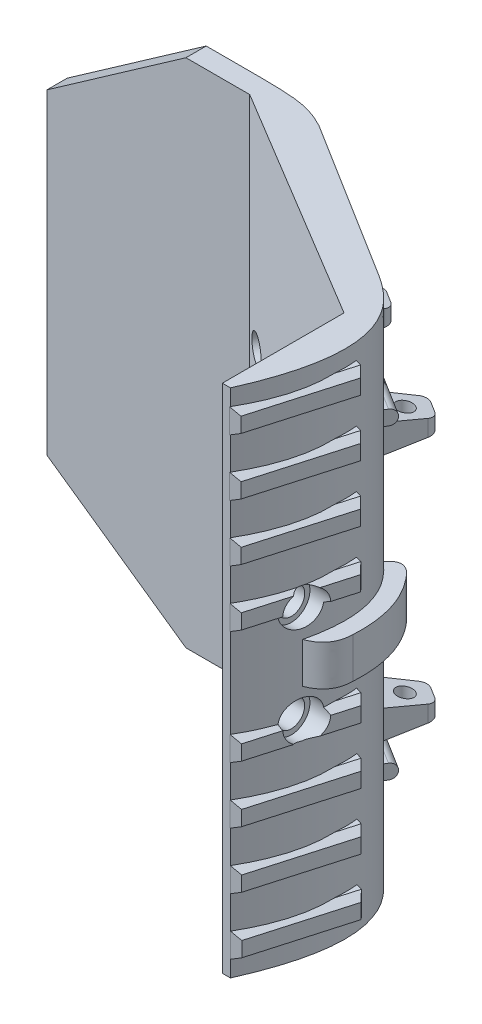
SolidWorks part; units mm, degrees
ref_plane "前视基准面" through (0, 0, 0) normal (0, 0, 1) x (1, 0, 0)
ref_plane "上视基准面" through (0, 0, 0) normal (0, 1, 0) x (1, 0, 0)
ref_plane "右视基准面" through (0, 0, 0) normal (1, 0, 0) x (0, 0, -1)
sketch "草图1" plane through (0, 0, 0) normal (0, 1, 0) x (1, 0, 0)
  line L5 (44.4388, -6.0197) -> (44.4388, -21.0197)
  line L6 (44.4388, -21.0197) -> (45.4388, -21.0197)
  line L7 (44.4388, -6.0197) -> (15.3139, 11.4803)
  line L8 (12.0784, 13.9803) -> (10.0784, 13.9803)
  line L9 (41.6518, 0.7146) -> (22.8495, 12.4582)
  line L10 (10.0784, 13.9803) -> (-9.6861, 13.9803)
  line L11 (-9.6861, 11.4803) -> (15.3139, 11.4803)
  line L12 (-9.6861, 13.9803) -> (-9.6861, 11.4803)
  line L13 (-35.8192, -203.5283) -> (126.6968, 161.4888) construction
  line L14 (85.2699, -26.5286) -> (-1.9663, 27.9577) construction
  spline S0 degree 3 poles (12.0784, 13.9803) (18.0822, 13.9803) (20.027, 13.9726) (22.8495, 12.4582) knots 0 0 0 0 0.428174 0.428174 0.428174 0.428174
  spline S1 degree 3 poles (41.6518, 0.7146) (45.3405, -1.5893) (52.3106, -5.5855) (45.4388, -21.0197) knots 0.746299 0.746299 0.746299 0.746299 1 1 1 1
  dimension "D3" = 121
  dimension "D2" = 20
  dimension "D6" = 114
  dimension "D7" = 180
  dimension "D1" = 1
  dimension "D4" = 2
  dimension "D5" = 35
  dimension "D8" = 2.5
  dimension "D9" = 25
extrude "凸台-拉伸1" add sketch "草图1" along normal blind 63
sketch "草图2" plane through (12.0098, 0, -19.2285) normal (0.5297, 0, -0.8482) x (-0.8482, 0, -0.5297)
  line L0 (-12.7803, 31.5) -> (-34.9487, 31.5) construction
  line L1 (-12.7803, 63) -> (-12.7803, 0) construction
  line L2 (-34.9487, 63) -> (-34.9487, 0) construction
  line L4 (-31.9487, 24.5) -> (-17.9487, 24.5)
  line L5 (-31.9487, 24.5) -> (-31.9487, 38.5)
  line L6 (-31.9487, 38.5) -> (-17.9487, 38.5)
  line L7 (-17.9487, 24.5) -> (-17.9487, 38.5)
  line L8 (-31.9487, 24.5) -> (-17.9487, 38.5) construction
  line L9 (-31.9487, 38.5) -> (-17.9487, 24.5) construction
  point P6 (-24.9487, 31.5)
  dimension "D1" = 14
  dimension "D2" = 14
  dimension "D3" = 3
extrude "凸台-拉伸2" add sketch "草图2" along normal blind 1 draft 25
sketch "草图6" plane through (0, 0, 0) normal (0, -1, 0) x (1, 0, 0)
  line L0 (13.0784, -13.9799) -> (24.6291, -11.9432)
  line L1 (15.3139, -11.4803) -> (44.4388, 6.0197) construction
  spline S0 degree 3 poles (22.8495, -12.4582) (20.027, -13.9726) (18.0822, -13.9803) (12.0784, -13.9803) knots 0 0 0 0 0.428174 0.428174 0.428174 0.428174 construction
  dimension "D1" = 21
  dimension "D2" = 1
ref_plane "基准面2" through (2.7851, 0, -15.7949) normal (0.1736, 0, -0.9848) x (0.9848, 0, 0.1736)
sketch "草图7" plane through (2.7851, 0, -15.7949) normal (0.1736, 0, -0.9848) x (0.9848, 0, 0.1736)
  line L1 (11.4673, -18.5) -> (22.4673, -18.5)
  line L2 (11.4673, -18.5) -> (11.4673, -44.5)
  line L3 (11.4673, -44.5) -> (22.4673, -44.5)
  line L4 (22.4673, -18.5) -> (22.4673, -44.5)
  line L5 (9.4673, -63) -> (9.4673, 0) construction
  line L7 (38.1132, -24.5) -> (25.1315, -24.5) construction
  line L8 (25.1315, -38.5) -> (38.1132, -38.5) construction
  dimension "D1" = 6
  dimension "D2" = 6
  dimension "D3" = 11
  dimension "D4" = 2
sketch "草图3" plane through (12.5395, 0, -20.0767) normal (0.5297, 0, -0.8482) x (-0.8482, 0, -0.5297)
  line L0 (-18.415, 31.5) -> (-31.4824, 31.5) construction
  line L1 (-18.415, 24.9663) -> (-18.415, 38.0337) construction
  line L2 (-31.4824, 38.0337) -> (-31.4824, 24.9663) construction
  line L3 (-24.9487, 38.0337) -> (-24.9487, 24.9663) construction
  line L4 (-18.415, 38.0337) -> (-31.4824, 38.0337) construction
  line L5 (-31.4824, 24.9663) -> (-18.415, 24.9663) construction
  line L6 (-21.7668, 34.682) -> (-28.1307, 28.318) construction
  line L7 (-20.7061, 33.6213) -> (-27.0701, 27.2574)
  line L8 (-22.8274, 35.7426) -> (-29.1914, 29.3787)
  line L9 (-21.7668, 28.318) -> (-28.1307, 34.682) construction
  line L10 (-22.8274, 27.2574) -> (-29.1914, 33.6213)
  line L11 (-20.7061, 29.3787) -> (-27.0701, 35.7426)
  arc A0 (-20.7061, 33.6213) -> (-22.8274, 35.7426) centre (-21.7668, 34.682) ccw
  arc A1 (-29.1914, 29.3787) -> (-27.0701, 27.2574) centre (-28.1307, 28.318) ccw
  arc A2 (-22.8274, 27.2574) -> (-20.7061, 29.3787) centre (-21.7668, 28.318) ccw
  arc A3 (-27.0701, 35.7426) -> (-29.1914, 33.6213) centre (-28.1307, 34.682) ccw
  point P14 (-24.9487, 31.5)
  point P19 (-24.9487, 31.5)
  dimension "D1" = 3
  dimension "D2" = 3
  dimension "D3" = 9
  dimension "D4" = 9
extrude "切除-拉伸1" cut sketch "草图3" against normal blind 0.6 contours L7 A0 L8 L11 | L7 L11 L8 L10 | L10 A2 L11 L7 | L8 A1 L7 L10 | L11 A3 L10 L8 region at (31.5395, 34.0473, -8.2096) region at (31.5395, 28.9527, -8.2096) region at (33.7, 31.5, -6.8602) region at (35.8605, 28.9527, -5.5108) region at (35.8605, 34.0473, -5.5108)
ref_plane "基准面1" through (10.1606, 0, -16.91) normal (-0.515, 0, 0.8572) x (0.8572, 0, 0.515)
extrude "凸台-拉伸4" add sketch "草图7" along normal blind 2 draft 35 and the other way blind 2
sketch "草图4" plane through (9.1305, 0, -15.1957) normal (-0.515, 0, 0.8572) x (0.8572, 0, 0.515)
  line L0 (41.1919, 31.5) -> (-14.9499, 31.5) construction
  line L1 (41.1919, 63) -> (41.1919, 0) construction
  line L2 (3.1528, 63) -> (3.1528, 0) construction
  circle A0 centre (9.6528, 25.5) radius 1.65
  circle A1 centre (9.6528, 37.5) radius 1.65
  dimension "D1" = 3.3
  dimension "D2" = 12
  dimension "D3" = 6.5
extrude "切除-拉伸2" cut sketch "草图4" against normal through all
sketch "草图5" plane through (10.1606, 0, -16.91) normal (-0.515, 0, 0.8572) x (0.8572, 0, 0.515)
  circle A0 centre (9.6528, 25.5) radius 2.3
  circle A1 centre (9.6528, 37.5) radius 2.3
  dimension "D1" = 4.6
extrude "切除-拉伸3" cut sketch "草图5" against normal through all
ref_plane "基准面3" through (2.7851, 0, -15.7949) normal (-0.1736, 0, 0.9848) x (0.9848, 0, 0.1736)
sketch "草图9" plane through (0, 0, 0) normal (0, -1, 0) x (1, 0, 0)
  line L0 (45.4388, 21.0197) -> (53.1155, -5.7522) construction
  line L1 (44.4388, 21.0197) -> (45.4388, 21.0197) construction
  dimension "D1" = 106
ref_plane "基准面4" through (47.5559, 0, 13.6364) normal (-0.9613, 0, -0.2756) x (-0.2756, 0, 0.9613)
sketch "草图10" plane through (47.5559, 0, 13.6364) normal (-0.9613, 0, -0.2756) x (-0.2756, 0, 0.9613)
  line L0 (-5.3616, 67.0628) -> (-5.3616, -5.3831) construction
  line L1 (7.6808, 63) -> (7.6808, 0) construction
  line L2 (-5.3616, 5) -> (7.6808, 5)
  line L3 (-5.3616, 5) -> (-5.3616, 2)
  line L4 (-5.3616, 2) -> (7.6808, 2)
  line L5 (7.6808, 5) -> (7.6808, 2)
  line L6 (-5.3514, 9) -> (7.691, 9)
  line L11 (-5.3514, 12) -> (7.691, 12)
  line L12 (-5.3514, 12) -> (-5.3514, 9)
  line L13 (7.691, 12) -> (7.691, 9)
  line L14 (-5.3514, 31.5) -> (-5.3514, 1.6169) construction
  line L15 (-5.3412, 16) -> (7.7012, 16)
  line L16 (-5.3412, 19) -> (7.7012, 19)
  line L17 (-5.3412, 19) -> (-5.3412, 16)
  line L18 (7.7012, 19) -> (7.7012, 16)
  line L19 (-5.3412, 31.5) -> (-5.3412, 8.6169) construction
  line L20 (-5.331, 23) -> (7.7115, 23)
  line L21 (-5.331, 26) -> (7.7115, 26)
  line L22 (-5.331, 26) -> (-5.331, 23)
  line L23 (7.7115, 26) -> (7.7115, 23)
  line L24 (-5.331, 31.5) -> (-5.331, 15.6169) construction
  line L25 (-5.3207, 30) -> (7.7217, 30)
  line L26 (-5.3207, 33) -> (7.7217, 33)
  line L27 (-5.3207, 33) -> (-5.3207, 30)
  line L28 (7.7217, 33) -> (7.7217, 30)
  line L29 (-5.3207, 33) -> (-5.3207, 22.6169) construction
  line L30 (-5.3105, 37) -> (7.7319, 37)
  line L31 (-5.3105, 40) -> (7.7319, 40)
  line L32 (-5.3105, 40) -> (-5.3105, 37)
  line L33 (7.7319, 40) -> (7.7319, 37)
  line L34 (-5.3105, 40) -> (-5.3105, 29.6169) construction
  line L35 (-5.3003, 44) -> (7.7421, 44)
  line L36 (-5.3003, 47) -> (7.7421, 47)
  line L37 (-5.3003, 47) -> (-5.3003, 44)
  line L38 (7.7421, 47) -> (7.7421, 44)
  line L39 (-5.3003, 47) -> (-5.3003, 36.6169) construction
  line L40 (-5.2901, 51) -> (7.7523, 51)
  line L41 (-5.2901, 54) -> (7.7523, 54)
  line L42 (-5.2901, 54) -> (-5.2901, 51)
  line L43 (7.7523, 54) -> (7.7523, 51)
  line L44 (-5.2901, 54) -> (-5.2901, 43.6169) construction
  line L45 (-5.2799, 58) -> (7.7625, 58)
  line L46 (-5.2799, 61) -> (7.7625, 61)
  line L47 (-5.2799, 61) -> (-5.2799, 58)
  line L48 (7.7625, 61) -> (7.7625, 58)
  line L49 (-5.2799, 61) -> (-5.2799, 50.6168) construction
  line L52 (7.6808, 31.5) -> (-12.1158, 31.5) construction
  point P9 (7.7217, 31.5)
  dimension "D1" = 3
  dimension "D2" = 9
extrude "凸台-拉伸6" add sketch "草图10" against normal blind 1 draft 30 contours L5 L2 L3 L4 | L13 L11 L12 L6 | L23 L21 L22 L20 | L38 L36 L37 L35 | L43 L41 L42 L40 | L48 L46 L47 L45 | L16 L18 L15 L17 | L31 L33 L30 L32 region at (47.2363, 3.5, 14.7511) region at (47.2335, 10.5, 14.761) region at (47.2278, 24.5, 14.7806) region at (47.2194, 45.5, 14.81) region at (47.2166, 52.5, 14.8198) region at (47.2138, 59.5, 14.8297)
sketch "草图11" plane through (47.5559, 0, 13.6364) normal (-0.9613, 0, -0.2756) x (-0.2756, 0, 0.9613)
  line L0 (-2.6974, 2) -> (-2.6974, 5) construction
  line L1 (-2.6974, 5) -> (-5.3616, 5) construction
  line L2 (-5.3616, 5) -> (-5.3616, 2) construction
  line L3 (-5.3616, 2) -> (-2.6974, 2) construction
  line L4 (-2.6974, 9) -> (-2.6974, 12) construction
  line L5 (-2.6974, 12) -> (-5.3514, 12) construction
  line L6 (-5.3514, 12) -> (-5.3514, 9) construction
  line L7 (-5.3514, 9) -> (-2.6974, 9) construction
  line L8 (-2.6974, 16) -> (-2.6974, 19) construction
  line L9 (-2.6974, 19) -> (-5.3412, 19) construction
  line L10 (-5.3412, 19) -> (-5.3412, 16) construction
  line L11 (-5.3412, 16) -> (-2.6974, 16) construction
  line L12 (-2.6974, 23) -> (-2.6974, 26) construction
  line L13 (-2.6974, 26) -> (-5.331, 26) construction
  line L14 (-5.331, 26) -> (-5.331, 23) construction
  line L15 (-5.331, 23) -> (-2.6974, 23) construction
  line L16 (-2.6974, 37) -> (-2.6974, 40) construction
  line L17 (-2.6974, 40) -> (-5.3105, 40) construction
  line L18 (-5.3105, 40) -> (-5.3105, 37) construction
  line L19 (-5.3105, 37) -> (-2.6974, 37) construction
  line L20 (-2.6974, 44) -> (-2.6974, 47) construction
  line L21 (-2.6974, 47) -> (-5.3003, 47) construction
  line L22 (-5.3003, 47) -> (-5.3003, 44) construction
  line L23 (-5.3003, 44) -> (-2.6974, 44) construction
  line L24 (-2.6974, 58) -> (-2.6974, 61) construction
  line L25 (-2.6974, 61) -> (-5.2799, 61) construction
  line L26 (-5.2799, 61) -> (-5.2799, 58) construction
  line L27 (-5.2799, 58) -> (-2.6974, 58) construction
  line L28 (-2.6974, 51) -> (-2.6974, 54) construction
  line L29 (-2.6974, 54) -> (-5.2901, 54) construction
  line L30 (-5.2901, 54) -> (-5.2901, 51) construction
  line L31 (-5.2901, 51) -> (-2.6974, 51) construction
  line L32 (-2.6974, 2) -> (-2.6974, 5)
  line L33 (-2.6974, 5) -> (-5.3616, 5)
  line L34 (-5.3616, 5) -> (-5.3616, 2)
  line L35 (-5.3616, 2) -> (-2.6974, 2)
  line L36 (-2.6974, 9) -> (-2.6974, 12)
  line L37 (-2.6974, 12) -> (-5.3514, 12)
  line L38 (-5.3514, 12) -> (-5.3514, 9)
  line L39 (-5.3514, 9) -> (-2.6974, 9)
  line L40 (-2.6974, 16) -> (-2.6974, 19)
  line L41 (-2.6974, 19) -> (-5.3412, 19)
  line L42 (-5.3412, 19) -> (-5.3412, 16)
  line L43 (-5.3412, 16) -> (-2.6974, 16)
  line L44 (-2.6974, 23) -> (-2.6974, 26)
  line L45 (-2.6974, 26) -> (-5.331, 26)
  line L46 (-5.331, 26) -> (-5.331, 23)
  line L47 (-5.331, 23) -> (-2.6974, 23)
  line L48 (-2.6974, 37) -> (-2.6974, 40)
  line L49 (-2.6974, 40) -> (-5.3105, 40)
  line L50 (-5.3105, 40) -> (-5.3105, 37)
  line L51 (-5.3105, 37) -> (-2.6974, 37)
  line L52 (-2.6974, 44) -> (-2.6974, 47)
  line L53 (-2.6974, 47) -> (-5.3003, 47)
  line L54 (-5.3003, 47) -> (-5.3003, 44)
  line L55 (-5.3003, 44) -> (-2.6974, 44)
  line L56 (-2.6974, 58) -> (-2.6974, 61)
  line L57 (-2.6974, 61) -> (-5.2799, 61)
  line L58 (-5.2799, 61) -> (-5.2799, 58)
  line L59 (-5.2799, 58) -> (-2.6974, 58)
  line L60 (-2.6974, 51) -> (-2.6974, 54)
  line L61 (-2.6974, 54) -> (-5.2901, 54)
  line L62 (-5.2901, 54) -> (-5.2901, 51)
  line L63 (-5.2901, 51) -> (-2.6974, 51)
extrude "凸台-拉伸7" add sketch "草图11" along normal up to surface (0.7956 mm away) up to face at (47.2407, 31.5, 13.7652)
sketch "草图12" plane through (44.4388, 0, 0) normal (-1, 0, 0) x (0, 0, 1)
  line L0 (21.0197, 31.5) -> (-9.4999, 31.5) construction
  line L1 (21.0197, 63) -> (21.0197, 0) construction
  line L2 (6.0197, 63) -> (6.0197, 0) construction
  circle A0 centre (14.5197, 25.5) radius 1.65
  circle A1 centre (14.5197, 37.5) radius 1.65
  dimension "D1" = 3.3
  dimension "D2" = 12
  dimension "D3" = 8.5
extrude "切除-拉伸4" cut sketch "草图12" against normal blind 2
sketch "草图13" plane through (46.4388, 0, 0) normal (-1, 0, 0) x (0, 0, 1)
  circle A0 centre (14.5197, 25.5) radius 2.3
  circle A1 centre (14.5197, 37.5) radius 2.3
  dimension "D1" = 4.6
extrude "切除-拉伸5" cut sketch "草图13" against normal through all
chamfer "倒角1" distance 12 angle 55 2 edges at (-9.6861, 63, -12.7303) (-9.6861, 0, -12.7303) first distance on face at (-9.6861, 31.5, -12.7303)
sketch "草图14" plane through (12.0098, 0, -19.2285) normal (0.5297, 0, -0.8482) x (-0.8482, 0, -0.5297)
  line L0 (-34.9487, 31.5) -> (5.0388, 31.5) construction
  line L1 (-34.9487, 63) -> (-34.9487, 0) construction
  line L2 (-34.9487, 63) -> (-12.7803, 63) construction
  line L3 (-27.7803, 54) -> (-17.7803, 54)
  line L4 (-27.7803, 54) -> (-27.7803, 59)
  line L5 (-27.7803, 59) -> (-17.7803, 59)
  line L6 (-17.7803, 54) -> (-17.7803, 59)
  line L7 (-12.7803, 63) -> (-12.7803, 44.3613) construction
  line L8 (-27.7803, 9) -> (-27.7803, 4)
  line L9 (-27.7803, 4) -> (-17.7803, 4)
  line L10 (-17.7803, 9) -> (-17.7803, 4)
  line L11 (-27.7803, 9) -> (-17.7803, 9)
  dimension "D1" = 5
  dimension "D2" = 10
  dimension "D3" = 4
  dimension "D4" = 5
extrude "凸台-拉伸8" add sketch "草图14" along normal blind 1 draft 25
sketch "草图15" plane through (12.0098, 0, -19.2285) normal (0.5297, 0, -0.8482) x (-0.8482, 0, -0.5297)
  line L0 (-34.9487, 31.5) -> (9.9606, 31.5) construction
  line L1 (-20.7803, 45) -> (-15.7803, 45)
  line L2 (-20.7803, 45) -> (-20.7803, 48.5)
  line L3 (-20.7803, 48.5) -> (-15.7803, 48.5)
  line L4 (-15.7803, 45) -> (-15.7803, 48.5)
  line L5 (-34.9487, 63) -> (-34.9487, 0) construction
  line L6 (-12.7803, 63) -> (-12.7803, 44.3613) construction
  line L7 (-26.7803, 63) -> (-26.7803, -8.1652) construction
  line L9 (-15.7803, 18) -> (-15.7803, 14.5)
  line L10 (-20.7803, 18) -> (-15.7803, 18)
  line L11 (-20.7803, 18) -> (-20.7803, 14.5)
  line L12 (-20.7803, 14.5) -> (-15.7803, 14.5)
  line L13 (-37.7803, 45) -> (-37.7803, 48.5)
  line L14 (-32.7803, 45) -> (-32.7803, 48.5)
  line L15 (-32.7803, 18) -> (-32.7803, 14.5)
  line L16 (-32.7803, 14.5) -> (-37.7803, 14.5)
  line L17 (-37.7803, 18) -> (-37.7803, 14.5)
  line L18 (-32.7803, 18) -> (-37.7803, 18)
  line L19 (-32.7803, 48.5) -> (-37.7803, 48.5)
  line L20 (-32.7803, 45) -> (-37.7803, 45)
  line L21 (-34.9487, 63) -> (-12.7803, 63) construction
  dimension "D1" = 5
  dimension "D2" = 3.5
  dimension "D3" = 3
  dimension "D4" = 14
  dimension "D5" = 14.5
extrude "凸台-拉伸9" add sketch "草图15" along normal blind 5 draft 10 and the other way blind 2
fillet "圆角1" radius 1 8 edges at (28.7904, 46.75, -14.6427) (31.5357, 46.75, -12.9281) (43.2091, 46.75, -5.6371) (45.9544, 46.75, -3.9224) (45.9544, 16.25, -3.9224) (43.2091, 16.25, -5.6371) (31.5357, 16.25, -12.9281) (28.7904, 16.25, -14.6427)
sketch "草图16" plane through (0, 0, 0) normal (0, 1, 0) x (1, 0, 0)
  line L0 (30.1631, 13.7854) -> (25.9473, 7.0356) construction
  line L1 (29.5021, 14.1982) -> (30.824, 13.3726) construction
  line L2 (44.5817, 4.7797) -> (40.3488, -1.9975) construction
  line L3 (43.9208, 5.1926) -> (45.2427, 4.3669) construction
  circle A0 centre (28.8387, 11.665) radius 1
  circle A1 centre (43.2574, 2.6594) radius 1
  point P12 (29.0565, 12.4217)
  point P13 (29.1954, 12.2362)
  point P14 (43.399, 2.8862)
  dimension "D1" = 2
  dimension "D2" = 2
  dimension "D3" = 2.5
  dimension "D4" = 2.5
extrude "切除-拉伸6" cut sketch "草图16" along normal through all
sketch "草图17" plane through (12.0098, 0, -19.2285) normal (0.5297, 0, -0.8482) x (-0.8482, 0, -0.5297)
  line L0 (-34.9487, 31.5) -> (6.1291, 31.5) construction
  line L1 (-26.7803, 13.5) -> (-39.7803, 13.5)
  line L2 (-26.7803, 13.5) -> (-26.7803, 11.7)
  line L3 (-26.7803, 11.7) -> (-39.7803, 11.7)
  line L4 (-39.7803, 13.5) -> (-39.7803, 11.7)
  line L5 (-34.9487, 45) -> (-34.9487, 18) construction
  line L6 (-39.7803, 49.5) -> (-39.7803, 51.3)
  line L7 (-26.7803, 49.5) -> (-39.7803, 49.5)
  line L8 (-26.7803, 49.5) -> (-26.7803, 51.3)
  line L9 (-26.7803, 51.3) -> (-39.7803, 51.3)
  line L10 (-32.7803, 14.5) -> (-32.7803, 18) construction
  dimension "D1" = 1.8
  dimension "D2" = 1
  dimension "D3" = 13
  dimension "D4" = 6
extrude "凸台-拉伸11" add sketch "草图17" along normal blind 0.9 and the other way blind 2
fillet "圆角2" radius 0.9 4 edges at (40.7135, 13.5, -2.3618) (40.7135, 11.7, -2.3618) (40.7135, 51.3, -2.3618) (40.7135, 49.5, -2.3618)
ref_plane "基准面5" through (0, 31.5, 0) normal (0, 1, 0) x (1, 0, 0)
sketch "草图18" plane through (0, 31.5, 0) normal (0, 1, 0) x (1, 0, 0)
  spline S1 degree 3 poles (-2387.6175, -1772.0297) (2651.7407, 1559.4695) (-2654.9556, -1405.9212) (2740.0926, 1311.014) knots -0.384486 -0.384486 -0.384486 -0.384486 2.333176 2.333176 2.333176 2.333176 only from (45.4388, -21.0197) to (41.6518, 0.7146) construction
  spline S2 degree 3 poles (-3005.2623, -2605.2202) (-307.3502, -397.975) (29.1624, -86.0457) (49.8109, -14.612) (50.1138, -13.0617) (50.3964, -10.2048) (50.3754, -8.8975) (50.0552, -6.507) (49.7551, -5.4246) (48.9463, -3.4899) (48.4383, -2.6389) (47.3169, -1.1574) (46.7045, -0.5263) (45.4744, 0.5594) (44.8565, 1.0148) (19.537, 18.2025) (66.7849, -79.2777) (3955.1185, 829.8997) knots -5.025966 -5.025966 -5.025966 -5.025966 0.125 0.125 0.25 0.25 0.375 0.375 0.5 0.5 0.625 0.625 0.75 0.75 0.875 0.875 6.228308 6.228308 6.228308 6.228308 only from (47.2659, -21.8332) to (42.7113, 2.4109)
  spline S3 degree 3 poles (50.319, -10.819) (50.3831, -9.7039) (50.3444, -8.6666) (50.0552, -6.507) (49.7551, -5.4246) (48.9463, -3.4899) (48.4383, -2.6389) (47.7898, -1.7822) (47.7008, -1.6688) (47.6106, -1.5582) knots 0.274144 0.274144 0.274144 0.274144 0.375 0.375 0.5 0.5 0.625 0.625 0.644573 0.644573 0.644573 0.644573
  spline S4 degree 3 poles (47.748, -14.4344) (49.5256, -6.9959) (47.0508, -3.3421) (44.3866, -1.1605) knots 0.787 0.787 0.787 0.787 0.944064 0.944064 0.944064 0.944064
  spline S5 degree 2 poles (50.319, -10.819) (50.2689, -13.4745) (47.748, -14.4344) knots 0 0 0 1 1 1
  spline S6 degree 2 poles (47.6106, -1.5582) (45.8268, 0.8118) (44.3866, -1.1605) knots 0 0 0 1 1 1
  point P9 (47.4345, -0.5949)
  point P11 (45.4388, -0.3113)
  point P12 (49.7131, -12.9604)
  point P13 (48.0223, -1.2424)
  point P14 (47.7227, -14.4344)
  dimension "D1" = 2
extrude "凸台-拉伸12" add sketch "草图18" along normal blind 2.5 and the other way blind 2.5
equation "\"M3_1\"= 3.3"
equation "\"D1@草图12\"=\"M3_1\""
equation "\"D1@草图4\"=\"M3_1\""
